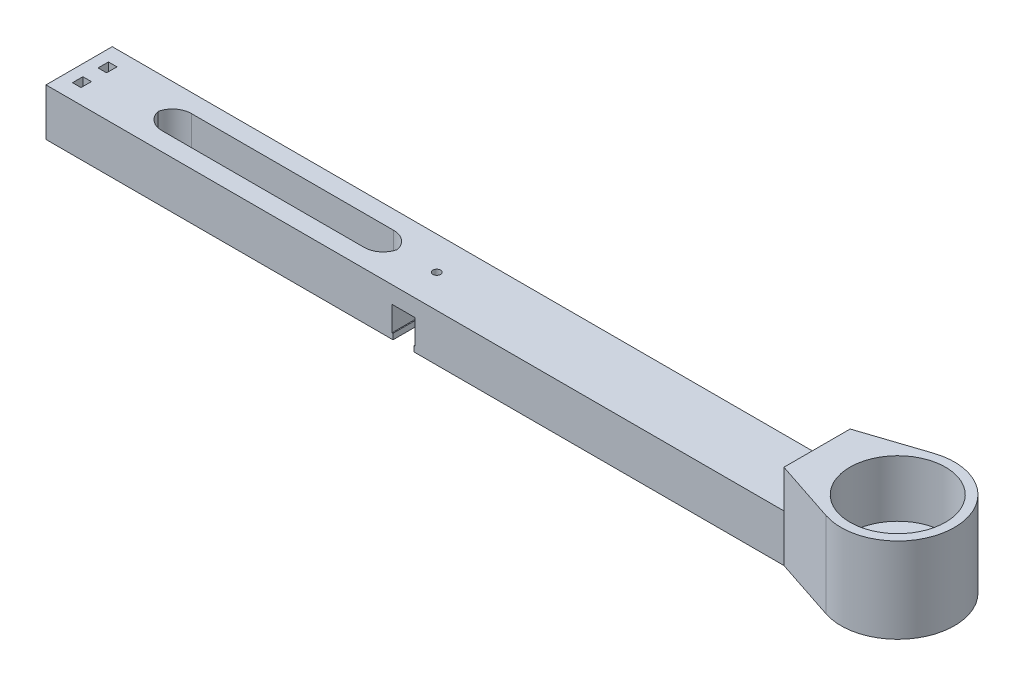
SolidWorks part; units mm, degrees
material "PLA "
ref_plane "Front Plane" through (0, 0, 0) normal (0, 0, 1) x (1, 0, 0)
ref_plane "Top Plane" through (0, 0, 0) normal (0, 1, 0) x (1, 0, 0)
ref_plane "Right Plane" through (0, 0, 0) normal (1, 0, 0) x (0, 0, -1)
sketch "Sketch1" plane through (0, 0, 0) normal (0, 1, 0) x (1, 0, 0)
  line L0 (0, 0) -> (-210, 0) construction
  line L1 (-210, 0) -> (-410, 0) construction
  dimension "D1" = 210
  dimension "D2" = 200
sketch "Sketch2" plane through (0, 0, 0) normal (0, 1, 0) x (1, 0, 0)
  line L1 (-210, -17.5) -> (0, -17.5)
  line L2 (-210, -17.5) -> (-210, 17.5)
  line L3 (-210, 17.5) -> (0, 17.5)
  line L4 (0, -17.5) -> (0, 17.5)
  point P4 (-210, 0)
  dimension "D1" = 35
extrude "Boss-Extrude1" add sketch "Sketch2" along normal blind 25 contours L1 L4 L3 L2
sketch "Sketch3" plane through (0, 0, 0) normal (0, -1, 0) x (1, 0, 0)
  line L0 (0, 0) -> (-21, 0) construction
  line L1 (0, 0) -> (-210, 0) construction
  circle A0 centre (-21, 0) radius 5.6
  dimension "D2" = 11.2
  dimension "D1" = 21
extrude "Cut-Extrude1" cut sketch "Sketch3" against normal through all
sketch "Sketch4" plane through (0, 25, 0) normal (0, 1, 0) x (1, 0, 0)
  line L0 (0, -17.5) -> (0, 17.5) construction
  line L1 (-14.9, 3.5218) -> (-21, 7.0437)
  line L2 (-21, 7.0437) -> (-27.1, 3.5218)
  line L3 (-27.1, 3.5218) -> (-27.1, -3.5218)
  line L4 (-27.1, -3.5218) -> (-21, -7.0437)
  line L5 (-21, -7.0437) -> (-14.9, -3.5218)
  line L6 (-14.9, -3.5218) -> (-14.9, 3.5218)
  line L7 (-27.1, 0) -> (-14.9, 0)
  circle A0 centre (-21, 0) radius 6.1 construction
  dimension "D1" = 12.2
extrude "Cut-Extrude2" cut sketch "Sketch4" against normal blind 22 contours L1 L2 L3 L4 L5 L6
sketch "Sketch6" plane through (0, 0, 0) normal (1, 0, 0) x (0, 0, -1)
  line L0 (0, 3) -> (0, 11) construction
  line L1 (-3.5218, 3) -> (3.5218, 3) construction
  line L2 (-17.5, 25) -> (17.5, 25) construction
  line L3 (-11.0435, 16) -> (11.453, 16)
  line L4 (-11.0435, 16) -> (-11.0435, 25)
  line L5 (-11.0435, 25) -> (11.453, 25)
  line L6 (11.453, 16) -> (11.453, 25)
  dimension "D1" = 8
extrude "Boss-Extrude3" add sketch "Sketch6" against normal blind 38
sketch "Sketch7" plane through (0, 0, 17.5) normal (0, 0, 1) x (1, 0, 0)
  line L0 (-21, 16) -> (-14.9, 16) construction
  line L1 (-27.1, 16) -> (-21, 16) construction
  line L2 (-27.1, 3) -> (-27.1, 16) construction
  line L3 (-14.9, 3) -> (-14.9, 16) construction
  line L4 (-15.4, 0) -> (-15.4, 3) construction
  line L5 (-26.6, 3) -> (-26.6, 0) construction
  line L6 (-21, 16) -> (-14.9, 16)
  line L7 (-27.1, 16) -> (-21, 16)
  line L8 (-27.1, 3) -> (-27.1, 16)
  line L9 (-14.9, 3) -> (-14.9, 16)
  line L10 (-15.4, 0) -> (-15.4, 3)
  line L11 (-26.6, 3) -> (-26.6, 0)
  line L12 (-27.1, 3) -> (-26.6, 3)
  line L13 (-15.4, 3) -> (-14.9, 3)
  line L14 (-26.6, 0) -> (-15.4, 0)
extrude "Cut-Extrude4" cut sketch "Sketch7" against normal up to vertex (17.5 mm away) up to point (-14.9, 25, 0)
sketch "Sketch9" plane through (0, 25, 0) normal (0, 1, 0) x (1, 0, 0)
  line L0 (-27.1, 3.5218) -> (-14.9, -3.5218) construction
  line L1 (-27.1, -3.5218) -> (-14.9, 3.5218) construction
  line L6 (-14.9, 3.5218) -> (-21, 7.0437)
  line L7 (-21, 7.0437) -> (-27.1, 3.5218)
  line L8 (-27.1, 3.5218) -> (-27.1, -3.5218)
  line L9 (-27.1, -3.5218) -> (-21, -7.0437)
  line L10 (-21, -7.0437) -> (-14.9, -3.5218)
  line L11 (-14.9, -3.5218) -> (-14.9, 3.5218)
  line L12 (-14.9, 3.5218) -> (-21, 7.0437) construction
  line L13 (-21, 7.0437) -> (-27.1, 3.5218) construction
  line L14 (-27.1, 3.5218) -> (-27.1, -3.5218) construction
  line L15 (-27.1, -3.5218) -> (-21, -7.0437) construction
  line L16 (-21, -7.0437) -> (-14.9, -3.5218) construction
  line L17 (-14.9, -3.5218) -> (-14.9, 3.5218) construction
  circle A0 centre (-21, 0) radius 2
  dimension "D2" = 4
  dimension "D1" = 0
extrude "Cut-Extrude5" cut sketch "Sketch9" against normal blind 38
sketch "Sketch10" plane through (-210, 0, 0) normal (-1, 0, 0) x (0, 0, 1)
  line L0 (-17.5, 25) -> (17.5, 0) construction
  line L2 (-7, 6) -> (7, 6) construction
  line L3 (-7, 6) -> (-7, 19) construction
  line L4 (-7, 19) -> (7, 19) construction
  line L5 (7, 6) -> (7, 19) construction
  line L6 (-7, 6) -> (7, 19) construction
  line L7 (-7, 19) -> (7, 6) construction
  circle A0 centre (7, 19) radius 2
  circle A1 centre (7, 6) radius 2
  circle A2 centre (-7, 6) radius 2
  circle A3 centre (-7, 19) radius 2
  point P4 (0, 12.5)
  dimension "D3" = 4
  dimension "D1" = 13
  dimension "D2" = 14
extrude "Cut-Extrude6" cut sketch "Sketch10" against normal blind 30
sketch "Sketch11" plane through (0, 25, 0) normal (0, 1, 0) x (1, 0, 0)
  line L0 (-210, 0) -> (-204, 0) construction
  line L1 (0, 0) -> (-210, 0) construction
  line L2 (-204, 0) -> (-204, -9) construction
  line L3 (-210, -9) -> (-180, -9) construction
  line L4 (-204, -9) -> (-200, -9) construction
  line L5 (-204, 0) -> (-204, 9) construction
  line L6 (-180, 9) -> (-210, 9) construction
  line L7 (-204, 9) -> (-200, 9) construction
  dimension "D1" = 6
  dimension "D2" = 4
  dimension "D3" = 4
sketch "Sketch12" plane through (0, 25, 0) normal (0, 1, 0) x (1, 0, 0)
  line L0 (-204, -9) -> (-204, -4.5) construction
  line L1 (-204, 0) -> (-204, -9) construction
  line L2 (-204, -9.5) -> (-204, -4)
  line L3 (-204, 4.5) -> (-204, 9) construction
  line L4 (-204, 0) -> (-204, 9) construction
  line L5 (-204, 4) -> (-204, 9.5)
  line L6 (-204, 9.5) -> (-199.5, 9.5)
  line L7 (-199.5, 9.5) -> (-199.5, 4)
  line L8 (-199.5, 4) -> (-204, 4)
  line L9 (-204, -4) -> (-199.5, -4)
  line L10 (-199.5, -4) -> (-199.5, -9.5)
  line L11 (-199.5, -9.5) -> (-204, -9.5)
  point P8 (-204, -6.75)
  point P16 (-204, 6.75)
  dimension "D1" = 5.5
  dimension "D2" = 4.5
extrude "Cut-Extrude7" cut sketch "Sketch12" against normal blind 46
sketch "Sketch14" plane through (0, 25, 0) normal (0, 1, 0) x (1, 0, 0)
  line L0 (-210, 0) -> (0, 0) construction
  line L1 (0, 0) -> (-210, 0) construction
  line L2 (-168.4751, 7.8098) -> (-41.5249, 7.8098)
  line L3 (-168.4751, 7.8098) -> (-168.4751, -7.8098)
  line L4 (-168.4751, -7.8098) -> (-41.5249, -7.8098)
  line L5 (-41.5249, 7.8098) -> (-41.5249, -7.8098)
  line L6 (-168.4751, 7.8098) -> (-41.5249, -7.8098) construction
  line L7 (-168.4751, -7.8098) -> (-41.5249, 7.8098) construction
  point P4 (-105, 0)
extrude "Cut-Extrude8" cut sketch "Sketch14" against normal blind 40
fillet "Fillet1" radius 10 4 edges at (-168.4751, 12.5, 7.8098) (-41.5249, 12.5, 7.8098) (-41.5249, 12.5, -7.8098) (-168.4751, 12.5, -7.8098)
sketch "Sketch17" plane through (0, 0, 0) normal (1, 0, 0) x (0, 0, -1)
  line L5 (17.5, 0) -> (17.5, 25)
  line L6 (17.5, 25) -> (-17.5, 25)
  line L7 (-17.5, 25) -> (-17.5, 0)
  line L8 (-17.5, 0) -> (17.5, 0)
  line L9 (17.5, 0) -> (17.5, 25)
  line L10 (17.5, 25) -> (-17.5, 25)
  line L11 (-17.5, 25) -> (-17.5, 0)
  line L12 (-17.5, 0) -> (17.5, 0)
  dimension "D1" = 0
extrude "Boss-Extrude5" add sketch "Sketch17" along normal blind 180
sketch "Sketch16" plane through (0, 25, 0) normal (0, 1, 0) x (1, 0, 0)
  line L2 (213.2317, 28.4843) -> (180, 17.5)
  line L3 (180, 17.5) -> (180, -17.5)
  line L4 (180, -17.5) -> (213.2317, -28.4843)
  line L6 (213.2317, 28.4843) -> (213.2317, -28.4843) construction
  arc A0 (213.2317, 28.4843) -> (213.2317, -28.4843) centre (222.6468, 0) cw
  point P0 (213.2317, 0)
  point P1 (180, 0)
  point P8 (252.6468, 0)
  dimension "D1" = 30
extrude "Boss-Extrude4" add sketch "Sketch16" against normal up to vertex (25 mm away) and the other way blind 20 contours A0 L4 L3 L2 up to point (180, 0, 17.5)
sketch "Sketch18" plane through (-210, 0, 0) normal (-1, 0, 0) x (0, 0, 1)
  line L0 (0, 25) -> (0, 0) construction
  line L1 (6.1, 25) -> (-6.1, 25) construction
  circle A0 centre (0, 12.5) radius 3.1304
extrude "Cut-Extrude9" cut sketch "Sketch18" against normal blind 10
sketch "Sketch20" plane through (0, 45, 0) normal (0, 1, 0) x (1, 0, 0)
  circle A0 centre (222.6468, 0) radius 25.25
  dimension "D1" = 50.5
extrude "Cut-Extrude11" cut sketch "Sketch20" against normal blind 30
equation "\"2.5c\"=10"
